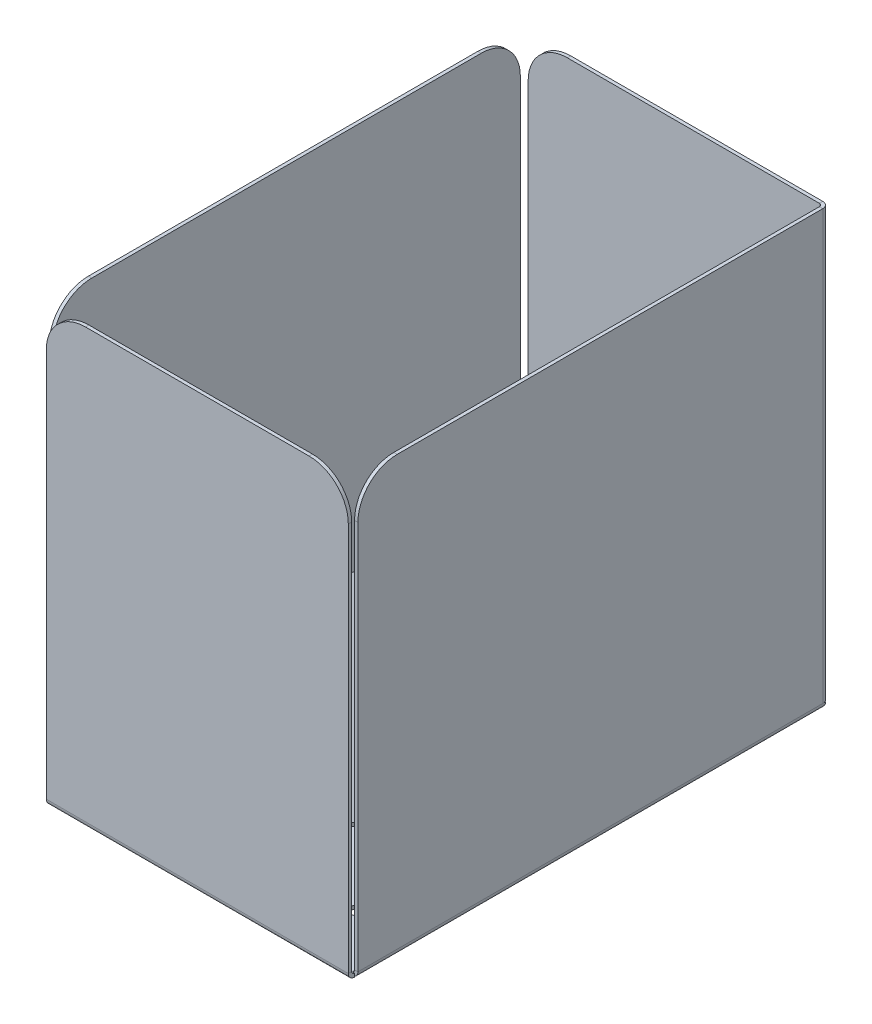
SolidWorks part; units mm, degrees
note: The reader was unsure of these and kept them because the rebuilt part matched: flange length of "Edge-Flange1", "Edge-Flange2", "Edge-Flange3", "Edge-Flange4", "Edge-Flange8".
ref_plane "Front Plane" through (0, 0, 0) normal (0, 0, 1) x (1, 0, 0)
ref_plane "Top Plane" through (0, 0, 0) normal (0, 1, 0) x (1, 0, 0)
ref_plane "Right Plane" through (0, 0, 0) normal (1, 0, 0) x (0, 0, -1)
sketch "Sketch1" plane through (0, 0, 0) normal (0, 1, 0) x (1, 0, 0)
  line L1 (38.5, -60) -> (-38.5, -60)
  line L2 (38.5, -60) -> (38.5, 60)
  line L3 (38.5, 60) -> (-38.5, 60)
  line L4 (-38.5, -60) -> (-38.5, 60)
  line L5 (38.5, -60) -> (-38.5, 60) construction
  line L6 (38.5, 60) -> (-38.5, -60) construction
  point P0 (0, 0)
  dimension "D1" = 120
  dimension "D2" = 77
base flange "Base-Flange1" sketch "Sketch1" thickness 0.86 reverse thickness direction no parameters "D1"=0.7366
ref_plane "Plane2" through (0, 0, 0) normal (1, 0, 0) x (0, 0, -1)
edge flange "Edge-Flange1" sketch "Sketch8" flange angle 90 flange length 110 flange position material outside bend radius 0.7366 thickness 0.86 parameters "D6"=10
sketch "Sketch8" plane through (0, 0, 60) normal (0, 0, 1) x (1, 0, 0)
  line L0 (-38.5, 0) -> (38.5, 0) construction
  line L1 (-38.5, 0) -> (38.5, 0)
  line L2 (-38.5, 0) -> (-38.5, 110)
  line L3 (-38.5, 110) -> (38.5, 110)
  line L4 (38.5, 110) -> (38.5, 0)
bend "EdgeBend1" bend radius 0.7366 bend angle 90 parameters "D5"=1
edge flange "Edge-Flange2" sketch "Sketch11" flange angle 90 flange length 110 flange position material outside bend radius 0.7366 thickness 0.86 parameters "D6"=10
sketch "Sketch11" plane through (38.5, 0, 0) normal (-1, 0, 0) x (0, 0, 1)
  line L1 (59.2634, 0) -> (-60, 0) construction
  line L2 (-60, 0) -> (-60, 110)
  line L3 (-60, 110) -> (59.2634, 110)
  line L4 (59.2634, 110) -> (59.2634, 0)
  line L5 (59.2634, 0) -> (-60, 0)
bend "EdgeBend2" bend radius 0.7366 bend angle 90 parameters "D5"=2
edge flange "Edge-Flange3" sketch "Sketch15" flange angle 90 flange length 110 flange position material outside bend radius 0.7366 thickness 0.86 parameters "D6"=10
sketch "Sketch15" plane through (-38.5, 0, 0) normal (-1, 0, 0) x (0, 0, 1)
  line L0 (-60, 0) -> (59.2634, 0) construction
  line L1 (-60, 0) -> (59.2634, 0)
  line L2 (-60, 0) -> (-60, 110)
  line L3 (-60, 110) -> (59.2634, 110)
  line L4 (59.2634, 110) -> (59.2634, 0)
bend "EdgeBend3" bend radius 0.7366 bend angle 90 parameters "D5"=3
edge flange "Edge-Flange4" sketch "Sketch18" flange angle 15 flange length 124 flange position material outside bend radius 0.7366 thickness 0.86 parameters "D6"=10
sketch "Sketch18" plane through (0, 0, -60) normal (0, -0.9659, 0.2588) x (1, 0, 0)
  line L1 (37.7634, 0) -> (-37.7634, 0) construction
  line L2 (-37.7634, 0) -> (-37.7634, 124)
  line L3 (-37.7634, 124) -> (37.7634, 124)
  line L4 (37.7634, 124) -> (37.7634, 0)
  line L5 (37.7634, 0) -> (-37.7634, 0)
bend "EdgeBend4" bend radius 0.7366 bend angle 165 parameters "D5"=4
edge flange "Edge-Flange8" sketch "Sketch39" flange angle 90 flange length 75 flange position material outside bend radius 0.7366 thickness 0.86 parameters "D6"=10
sketch "Sketch39" plane through (38.5, 0, -60) normal (0, 0, 1) x (0, 1, 0)
  line L1 (110, 0) -> (0.7366, 0) construction
  line L2 (0.7366, 0) -> (0.7366, 75)
  line L3 (0.7366, 75) -> (110, 75)
  line L4 (110, 75) -> (110, 0)
  line L5 (110, 0) -> (0.7366, 0)
bend "EdgeBend9" bend radius 0.7366 bend angle 90 parameters "D5"=5
hole_wizard "M3 Clearance Hole3" positions "Sketch47" profile "Sketch46" hole size "M3" standard "ANSI Metric"
sketch "Sketch47" plane through (0, -0.86, 0) normal (0, -1, 0) x (-1, 0, 0)
  point P0 (-25, 45)
  point P2 (25, 45)
  point P4 (25, -45)
  point P6 (-25, -45)
sketch "Sketch46" plane through (25, -0.86, -45) normal (1, 0, 0) x (0, 0, -1)
  line L0 (0, 0) -> (0, 26.4215)
  line L1 (0, 26.4215) -> (1.7, 25.4)
  line L2 (1.7, 25.4) -> (1.7, 0)
  line L5 (1.7, 0) -> (0, 0)
  line L10 (0, 26.4215) -> (-1.7, 25.4) construction
  line L11 (0, -6.35) -> (0, 107.95) construction
  dimension "Hole Dia." = 3.4
  dimension "Hole Depth" = 25.4
  dimension "Drill Angle" = 118
fillet "Fillet1" radius 10 7 edges at (-36.5, 0.7366, -60.43) (-36.5, 110, -60.43) (-38.93, 110, -60) (-38.93, 110, 59.2634) (38.93, 110, 59.2634) (38.5, 110, 60.43) (-38.5, 110, 60.43)
sketch "Bend-Lines1" plane through (0, 0, 0) normal (0, 1, 0) x (1, 0, 0)
sketch "Bounding-Box1" plane through (0, 0, 0) normal (0, 1, 0) x (1, 0, 0)
sheet metal parameters "Sheet-Metal(1)" thickness 0.86 parameters "D1"=0.7366
flat pattern "Flat-Pattern(1)" [suppressed]
sketch "Bend-Lines2" plane through (0, 0, 0) normal (0, 1, 0) x (1, 0, 0)
sketch "Bounding-Box2" [suppressed] plane through (0, 0, 0) normal (0, 1, 0) x (1, 0, 0)
sheet metal parameters "Sheet-Metal(2)" thickness 0.86 parameters "D1"=0.7366
flat pattern "Flat-Pattern(1)" [suppressed]
sketch "Bend-Lines2" plane through (0, 0, 0) normal (0, 1, 0) x (1, 0, 0)
sketch "Bounding-Box2" [suppressed] plane through (0, 0, 0) normal (0, 1, 0) x (1, 0, 0)
bend of the flat pattern "Flatten-<EdgeBend1>1"
sheet metal parameters "Sheet-Metal(3)" thickness 0.86 parameters "D1"=0.7366
flat pattern "Flat-Pattern(1)" [suppressed]
sketch "Bend-Lines2" plane through (0, 0, 0) normal (0, 1, 0) x (1, 0, 0)
sketch "Bounding-Box2" [suppressed] plane through (0, 0, 0) normal (0, 1, 0) x (1, 0, 0)
bend of the flat pattern "Flatten-<EdgeBend1>1"
bend of the flat pattern "Flatten-<EdgeBend2>1"
sheet metal parameters "Sheet-Metal(4)" thickness 0.86 parameters "D1"=0.7366
flat pattern "Flat-Pattern(1)" [suppressed]
sketch "Bend-Lines2" plane through (0, 0, 0) normal (0, 1, 0) x (1, 0, 0)
sketch "Bounding-Box2" [suppressed] plane through (0, 0, 0) normal (0, 1, 0) x (1, 0, 0)
bend of the flat pattern "Flatten-<EdgeBend1>1"
bend of the flat pattern "Flatten-<EdgeBend2>1"
bend of the flat pattern "Flatten-<EdgeBend3>1"
sheet metal parameters "Sheet-Metal(7)" thickness 0.86 parameters "D1"=0.7366
flat pattern "Flat-Pattern(1)" [suppressed]
sketch "Bend-Lines2" plane through (0, 0, 0) normal (0, 1, 0) x (1, 0, 0)
sketch "Bounding-Box2" [suppressed] plane through (0, 0, 0) normal (0, 1, 0) x (1, 0, 0)
bend of the flat pattern "Flatten-<EdgeBend1>1"
bend of the flat pattern "Flatten-<EdgeBend2>1"
bend of the flat pattern "Flatten-<EdgeBend3>1"
bend of the flat pattern "Flatten-<EdgeBend4>1"
sheet metal parameters "Sheet-Metal(11)" thickness 0.86 parameters "D1"=0.7366
flat pattern "Flat-Pattern(1)" [suppressed]
sketch "Bend-Lines2" plane through (0, 0, 0) normal (0, 1, 0) x (1, 0, 0)
sketch "Bounding-Box2" [suppressed] plane through (0, 0, 0) normal (0, 1, 0) x (1, 0, 0)
bend of the flat pattern "Flatten-<EdgeBend1>1"
bend of the flat pattern "Flatten-<EdgeBend2>1"
bend of the flat pattern "Flatten-<EdgeBend3>1"
bend of the flat pattern "Flatten-<EdgeBend4>1"
bend of the flat pattern "Flatten-<EdgeBend9>1"
sheet metal parameters "Sheet-Metal(14)" thickness 0.86 parameters "D1"=0.7366
flat pattern "Flat-Pattern(1)" [suppressed]
sketch "Bend-Lines2" plane through (0, 0, 0) normal (0, 1, 0) x (1, 0, 0)
sketch "Bounding-Box2" [suppressed] plane through (0, 0, 0) normal (0, 1, 0) x (1, 0, 0)
bend of the flat pattern "Flatten-<EdgeBend1>1"
bend of the flat pattern "Flatten-<EdgeBend2>1"
bend of the flat pattern "Flatten-<EdgeBend3>1"
bend of the flat pattern "Flatten-<EdgeBend4>1"
bend of the flat pattern "Flatten-<EdgeBend9>1"
